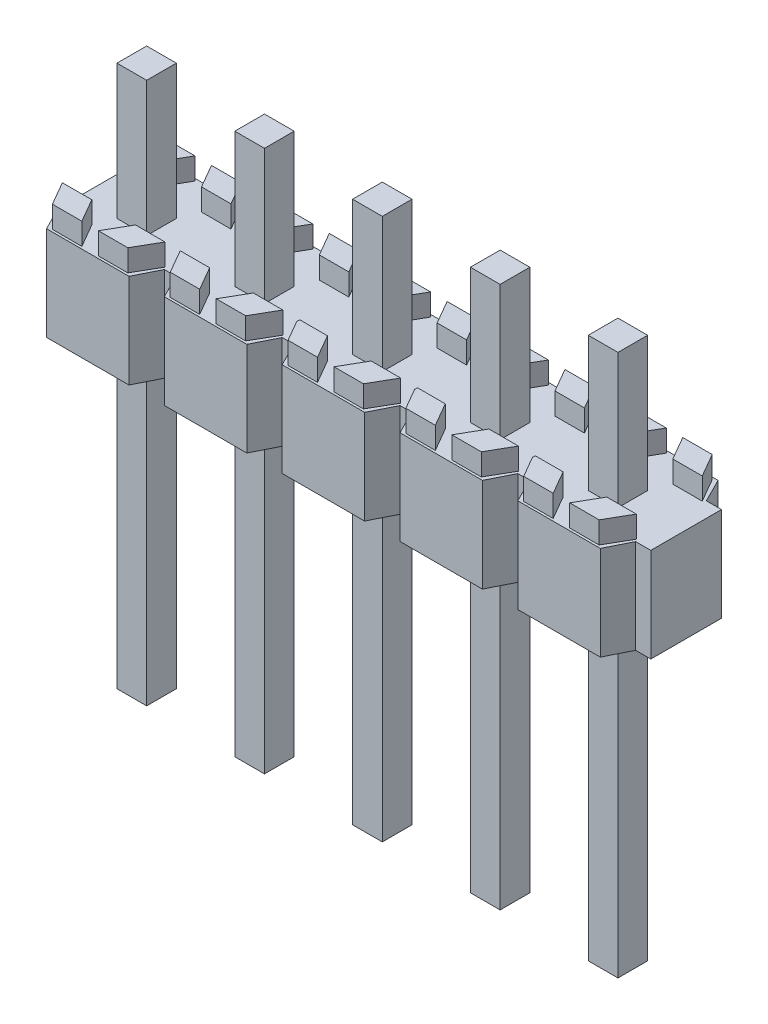
SolidWorks part; units mm, degrees
ref_plane "Front Plane" through (0, 0, 0) normal (0, 0, 1) x (1, 0, 0)
ref_plane "Top Plane" through (0, 0, 0) normal (0, 1, 0) x (1, 0, 0)
ref_plane "Right Plane" through (0, 0, 0) normal (1, 0, 0) x (0, 0, -1)
sketch "Sketch1" plane through (0, 0, 0) normal (0, 1, 0) x (1, 0, 0)
  line L0 (0, 1.5791) -> (0, -1.5527) construction
  line L2 (-0.32, 0.32) -> (0.32, 0.32)
  line L3 (-0.32, 0.32) -> (-0.32, -0.32)
  line L4 (-0.32, -0.32) -> (0.32, -0.32)
  line L5 (0.32, 0.32) -> (0.32, -0.32)
  line L6 (-0.32, 0.32) -> (0.32, -0.32) construction
  line L7 (-0.32, -0.32) -> (0.32, 0.32) construction
  line L8 (-1.143, 0.762) -> (-0.889, 1.27)
  line L9 (-0.889, 1.27) -> (0.889, 1.27)
  line L10 (0.889, 1.27) -> (1.143, 0.762)
  line L11 (1.143, 0.762) -> (1.47, 0.762)
  line L12 (1.47, 0.762) -> (1.47, -0.762)
  line L13 (1.47, -0.762) -> (1.143, -0.762)
  line L14 (1.143, -0.762) -> (0.889, -1.27)
  line L15 (0.889, -1.27) -> (-0.889, -1.27)
  line L16 (-0.889, -1.27) -> (-1.143, -0.762)
  line L17 (-1.143, -0.762) -> (-1.143, 0.762)
  line L18 (-1.7519, 0.762) -> (1.5375, 0.762) construction
  line L19 (1.0554, 0) -> (-1.5628, 0) construction
  line L20 (-1.697, -0.762) -> (2.4529, -0.762) construction
  point P3 (0, 0)
  dimension "D1" = 0.64
  dimension "D2" = 0.64
  dimension "D3" = 0.889
  dimension "D4" = 1.778
  dimension "D5" = 1.27
  dimension "D6" = 1.143
  dimension "D7" = 0.762
  dimension "D8" = 1.47
extrude "Boss-Extrude1" add sketch "Sketch1" along normal blind 1.48 and the other way blind 1.02
sketch "Sketch2" plane through (0, 1.48, 0) normal (0, 1, 0) x (1, 0, 0)
  line L0 (-1.1061, -0.7112) -> (-0.4711, -0.7112)
  line L1 (-0.4711, -0.7112) -> (-0.1778, -1.2192)
  line L2 (-0.1778, -1.2192) -> (-0.8128, -1.2192)
  line L3 (-1.143, 0.762) -> (-1.143, -0.762) construction
  line L4 (-0.889, 1.27) -> (-1.143, 0.762) construction
  line L5 (-0.8128, -1.2192) -> (-1.1061, -0.7112)
  line L6 (0, 1.3694) -> (0, -1.4569) construction
  line L7 (-1.5186, 0) -> (1.896, 0) construction
  line L8 (-0.8128, 1.2192) -> (-1.1061, 0.7112)
  line L9 (-0.1778, 1.2192) -> (-0.8128, 1.2192)
  line L10 (-0.4711, 0.7112) -> (-0.1778, 1.2192)
  line L11 (-1.1061, 0.7112) -> (-0.4711, 0.7112)
  line L12 (1.1061, 0.7112) -> (0.4711, 0.7112)
  line L13 (0.4711, 0.7112) -> (0.1778, 1.2192)
  line L14 (0.1778, 1.2192) -> (0.8128, 1.2192)
  line L15 (0.8128, 1.2192) -> (1.1061, 0.7112)
  line L16 (0.8128, -1.2192) -> (1.1061, -0.7112)
  line L17 (0.1778, -1.2192) -> (0.8128, -1.2192)
  line L18 (0.4711, -0.7112) -> (0.1778, -1.2192)
  line L19 (1.1061, -0.7112) -> (0.4711, -0.7112)
  line L20 (0.889, 1.27) -> (-0.889, 1.27) construction
  line L21 (1.143, 0.762) -> (0.889, 1.27) construction
  line L22 (1.47, 0.762) -> (1.143, 0.762) construction
  line L23 (1.47, -0.762) -> (1.47, 0.762) construction
  line L24 (1.143, -0.762) -> (1.47, -0.762) construction
  line L25 (0.889, -1.27) -> (1.143, -0.762) construction
  line L26 (-0.889, -1.27) -> (0.889, -1.27) construction
  line L27 (-1.143, -0.762) -> (-0.889, -1.27) construction
  line L28 (-1.143, 0.762) -> (-1.143, -0.762)
  line L29 (-0.889, 1.27) -> (-1.143, 0.762)
  line L30 (0.889, 1.27) -> (-0.889, 1.27)
  line L31 (1.143, 0.762) -> (0.889, 1.27)
  line L32 (1.47, 0.762) -> (1.143, 0.762)
  line L33 (1.47, -0.762) -> (1.47, 0.762)
  line L34 (1.143, -0.762) -> (1.47, -0.762)
  line L35 (0.889, -1.27) -> (1.143, -0.762)
  line L36 (-0.889, -1.27) -> (0.889, -1.27)
  line L37 (-1.143, -0.762) -> (-0.889, -1.27)
extrude "Cut-Extrude2" cut sketch "Sketch2" against normal blind 0.47
sketch "Sketch3" plane through (0, 1.01, 0) normal (0, 1, 0) x (1, 0, 0)
  line L4 (-0.32, 0.32) -> (0.32, 0.32)
  line L5 (0.32, 0.32) -> (0.32, -0.32)
  line L6 (0.32, -0.32) -> (-0.32, -0.32)
  line L7 (-0.32, -0.32) -> (-0.32, 0.32)
extrude "Boss-Extrude2" add sketch "Sketch3" along normal blind 2.9 separate body
sketch "Sketch4" plane through (0, -1.02, 0) normal (0, -1, 0) x (1, 0, 0)
  line L4 (-0.32, -0.32) -> (0.32, -0.32)
  line L5 (0.32, -0.32) -> (0.32, 0.32)
  line L6 (0.32, 0.32) -> (-0.32, 0.32)
  line L7 (-0.32, 0.32) -> (-0.32, -0.32)
  line L8 (-0.32, -0.32) -> (0.32, -0.32)
  line L9 (0.32, -0.32) -> (0.32, 0.32)
  line L10 (0.32, 0.32) -> (-0.32, 0.32)
  line L11 (-0.32, 0.32) -> (-0.32, -0.32)
  dimension "D1" = 0
extrude "Boss-Extrude3" add sketch "Sketch4" along normal blind 6.75 separate body
pattern_linear "LPattern1" count 5 spacing 2.54 along (1, 0, 0) of "Boss-Extrude1", "Cut-Extrude2", "Boss-Extrude2", "Boss-Extrude3"
